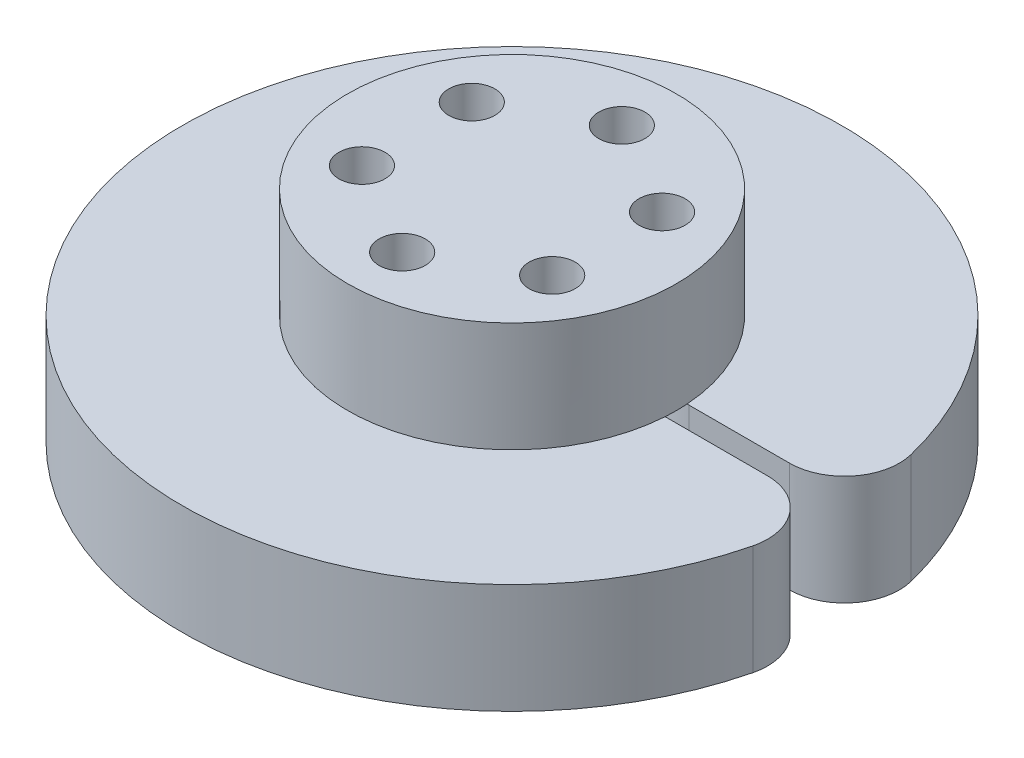
SolidWorks part; units mm, degrees
ref_plane "前视基准面" through (0, 0, 0) normal (0, 0, 1) x (1, 0, 0)
ref_plane "上视基准面" through (0, 0, 0) normal (0, 1, 0) x (1, 0, 0)
ref_plane "右视基准面" through (0, 0, 0) normal (1, 0, 0) x (0, 0, -1)
other "Configuration Table"
sketch "草图1" plane through (0, 0, 0) normal (0, 1, 0) x (1, 0, 0)
  circle A0 centre (0, 0) radius 30
  dimension "D1" = 60
extrude "凸台-拉伸1" add sketch "草图1" along normal blind 10
sketch "草图2" plane through (0, 10, 0) normal (0, 1, 0) x (1, 0, 0)
  circle A0 centre (0, 0) radius 14.975
  dimension "D1" = 29.95
extrude "凸台-拉伸2" add sketch "草图2" along normal blind 10
sketch "草图3" plane through (0, 0, 0) normal (0, -1, 0) x (1, 0, 0)
  circle A0 centre (0, 0) radius 14.975
  dimension "D1" = 29.95
extrude "凸台-拉伸3" add sketch "草图3" along normal blind 6
sketch "草图4" plane through (0, -6, 0) normal (0, -1, 0) x (1, 0, 0)
  circle A0 centre (0, 0) radius 10 construction
  circle A1 centre (-10, 0) radius 2.1
  circle A2 centre (-5, 8.6603) radius 2.1
  circle A3 centre (5, 8.6603) radius 2.1
  circle A5 centre (5, -8.6603) radius 2.1
  circle A6 centre (-5, -8.6603) radius 2.1
  circle A7 centre (10, 0) radius 2.1 [skipped]
  point P11 (0, 0)
  dimension "D1" = 20
  dimension "D2" = 4.2
  dimension "D3" = 6
extrude "切除-拉伸1" cut sketch "草图4" against normal blind 16
sketch "草图6" plane through (0, 10, 0) normal (0, 1, 0) x (1, 0, 0)
  line L0 (10.9343, 1) -> (10.9343, -1) construction
  line L1 (10.9343, 1) -> (30.9343, 1)
  line L3 (10.9343, -1) -> (30.9343, -1)
  line L4 (30.9343, 1) -> (30.9343, -1)
  arc A0 (10.9343, 1) -> (10.9343, -1) centre (8, 0) ccw
  dimension "D1" = 6.2
  dimension "D2" = 8
  dimension "D3" = 2
  dimension "D4" = 20
extrude "切除-拉伸3" cut sketch "草图6" against normal through all
fillet "圆角1" radius 10 2 edges at (10.9343, 2, -1) (10.9343, 2, 1)
fillet "圆角2" radius 5 2 edges at (29.9833, 5, -1) (29.9833, 5, 1)
fillet "圆角3" radius 0.2 2 edges at (14.9415, -3, 1.0015) (14.9415, -3, -1.0015)
sketch "草图7" plane through (0, 10, 0) normal (0, -1, 0) x (1, 0, 0)
  circle A0 centre (8, 0) radius 1.25
  dimension "D1" = 2.5
extrude "切除-拉伸4" cut sketch "草图7" against normal blind 8
sketch "草图8" plane through (0, 20, 0) normal (0, 1, 0) x (1, 0, 0)
  line L0 (0, 0) -> (-8.6603, 5) construction
  line L1 (0, 0) -> (0, 10) construction
  circle A0 centre (0, 0) radius 10 construction
  circle A1 centre (-8.6603, 5) radius 2.1
  circle A2 centre (0, 10) radius 2.1
  circle A3 centre (8.6603, 5) radius 2.1
  circle A4 centre (8.6603, -5) radius 2.1
  circle A5 centre (0, -10) radius 2.1
  circle A6 centre (-8.6603, -5) radius 2.1
  point P17 (0, 0)
  dimension "D1" = 20
  dimension "D2" = 4.2
  dimension "D4" = 60
  dimension "D3" = 6
extrude "切除-拉伸5" cut sketch "草图8" against normal blind 5
